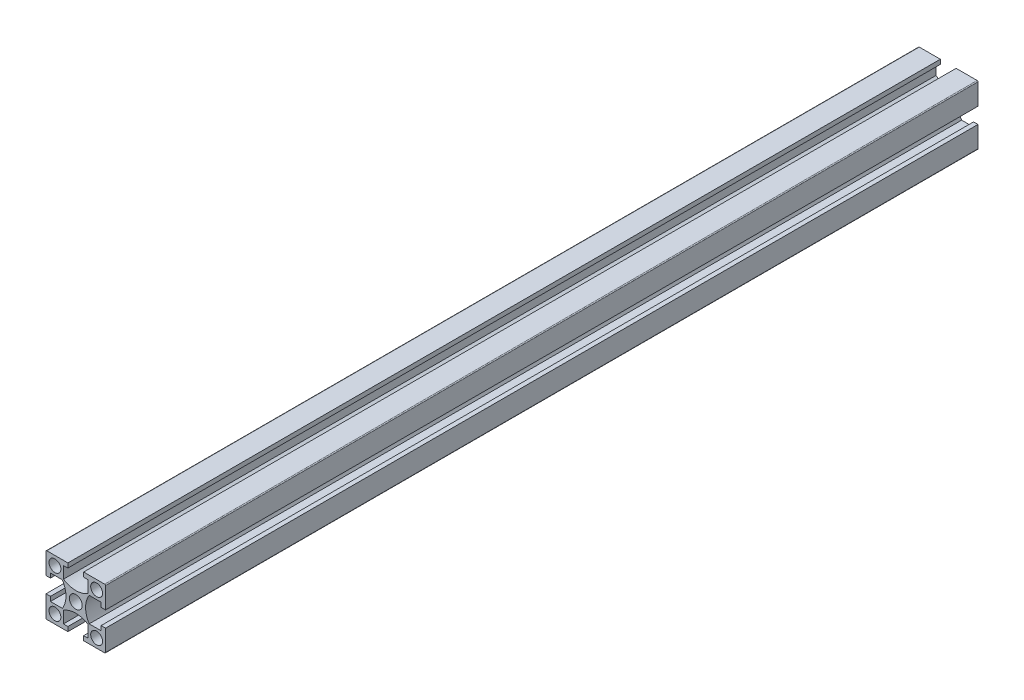
SolidWorks part; units mm, degrees
ref_plane "정면" through (0, 0, 0) normal (0, 0, 1) x (1, 0, 0)
ref_plane "윗면" through (0, 0, 0) normal (0, 1, 0) x (1, 0, 0)
ref_plane "우측면" through (0, 0, 0) normal (1, 0, 0) x (0, 0, -1)
sketch "스케치1" plane through (0, 0, 0) normal (0, 0, 1) x (1, 0, 0)
  line L0 (0, 32.0265) -> (0, -31.6588) construction
  line L1 (-10, 10) -> (-10, -10)
  line L2 (-10, 10) -> (10, 10)
  line L3 (-10, 2.65) -> (-8.5, 2.65)
  line L4 (13.6618, 0) -> (-11.6993, 0) construction
  line L5 (-8.5, 2.65) -> (-8.5, 4.15)
  line L6 (-8.5, 4.15) -> (-4.5032, 4.15)
  line L7 (-10, -2.65) -> (-8.5, -2.65)
  line L8 (-8.5, -2.65) -> (-8.5, -4.15)
  line L9 (-8.5, -4.15) -> (-4.5032, -4.15)
  line L10 (-10, -10) -> (10, -10)
  line L11 (10, 10) -> (10, -10)
  circle A0 centre (-7, 7) radius 2
  circle A1 centre (-7, -7) radius 2
  arc A2 (-4.5032, 4.15) -> (-4.5032, -4.15) centre (-11.0587, 0) cw
  circle A3 centre (0, 0) radius 2.15
  circle A4 centre (7, 7) radius 2
  circle A5 centre (7, -7) radius 2
  point P21 (-10, 0)
  point P23 (-3.3, 0)
  point P31 (0, -10)
  point P32 (0, 10)
  dimension "D3" = 4
  dimension "D9" = 6.7
  dimension "D10" = 4.3
  dimension "D11" = 7.7587
  dimension "D1" = 20
  dimension "D2" = 20
  dimension "D4" = 14
  dimension "D5" = 14
  dimension "D6" = 5.3
  dimension "D7" = 8.3
  dimension "D8" = 1.5
extrude "보스-돌출1" add sketch "스케치1" along normal blind 293 contours A0 | A4 | A3 | A5 | A1 | A2 L6 L5 L3 L1 L7 L8 L9 | L2 L11 L10 L1 region at (-6.6069, 0, 0) region at (-7, 7, 0) region at (-7, -7, 0) region at (0, 0, 0) region at (7, 7, 0) region at (7, -7, 0)
extrude "컷-돌출1" cut sketch "스케치1<3>" along normal up to next contours A2 L6 L5 L3 L1 L7 L8 L9 region at (-6.6069, 0, 0)
sketch "스케치1<3>" plane through (0, 0, 0) normal (0, 0, 1) x (1, 0, 0) same geometry as "스케치1"
pattern_circular "원형 패턴1" count 4 over 360 about axis through (0, 0, 293) along (0, 0, -1) of "컷-돌출1" reverse direction yes
fillet "필렛1" radius 0.3 4 edges at (10, -10, 146.5) (-10, -10, 146.5) (-10, 10, 146.5) (10, 10, 146.5)
sketch "스케치2" plane through (0, 0, 0) normal (1, 0, 0) x (0, 0, -1)
  circle A0 centre (-25, 0) radius 2.5
  dimension "D1" = 5
  dimension "D2" = 25
extrude "컷-돌출2" cut sketch "스케치2" against normal through all both and the other way through all
sketch "스케치4" plane through (0, 10, 0) normal (0, 1, 0) x (1, 0, 0)
  line L0 (0, -11) -> (0, 11) construction
  line L2 (2.65, -293) -> (9.7, -293) construction
  line L3 (-2.65, -106.62) -> (2.65, -106.62) construction
  line L4 (-2.65, -293) -> (-2.65, 0) construction
  line L5 (2.65, -293) -> (2.65, 0) construction
  line L6 (2.65, 0) -> (9.7, 0) construction
  circle A1 centre (0, -282) radius 2.5
  circle A2 centre (0, -127.62) radius 2.5
  circle A3 centre (0, -85.62) radius 2.5
  dimension "D1" = 21
  dimension "D2" = 11
  dimension "D3" = 106.62
  dimension "D4" = 21
extrude "컷-돌출3" cut sketch "스케치4" against normal through all
sketch "스케치6" plane through (0, 10, 0) normal (0, 1, 0) x (1, 0, 0)
  line L0 (0, -11) -> (0, 11) construction
  line L1 (4.15, 0) -> (-4.15, 0) construction
  circle A0 centre (0, -236.9) radius 2.15
  circle A1 centre (0, -184.9) radius 2.15
  circle A2 centre (0, -10.15) radius 1.9797
  circle A3 centre (0, -62.15) radius 2.15
  dimension "D1" = 56.1
  dimension "D2" = 52
  dimension "D4" = 52
  dimension "D3" = 10.15
extrude "컷-돌출4" cut sketch "스케치6" against normal through all
